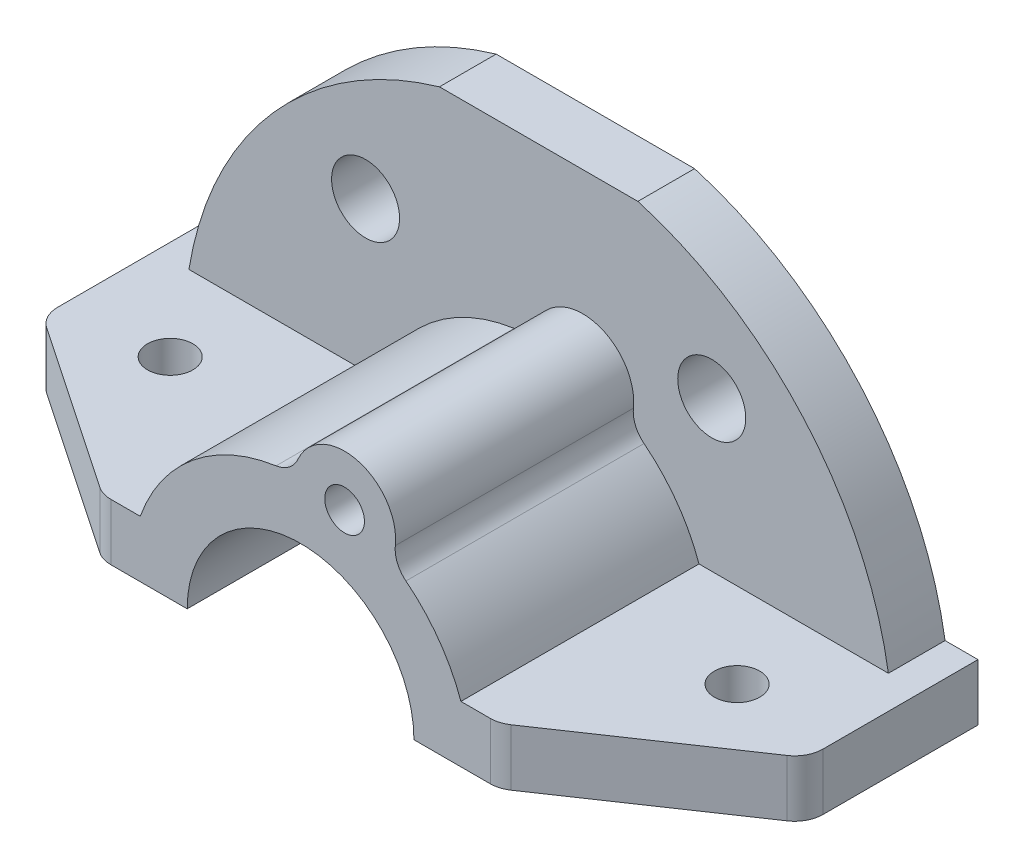
SolidWorks part; units mm, degrees
ref_plane "Front Plane" through (0, 0, 0) normal (0, 0, 1) x (1, 0, 0)
ref_plane "Top Plane" through (0, 0, 0) normal (0, 1, 0) x (1, 0, 0)
ref_plane "Right Plane" through (0, 0, 0) normal (1, 0, 0) x (0, 0, -1)
sketch "Sketch2" plane through (0, 0, 0) normal (0, 1, 0) x (1, 0, 0)
  line L0 (-67.5, -4) -> (-35, -26)
  line L1 (-67.5, -26) -> (67.5, -26)
  line L2 (-67.5, -26) -> (-67.5, 26)
  line L3 (-67.5, 26) -> (67.5, 26)
  line L4 (67.5, -26) -> (67.5, 26)
  line L5 (-67.5, -26) -> (67.5, 26) construction
  line L6 (-67.5, 26) -> (67.5, -26) construction
  line L7 (0, 0) -> (0, -19.8926) construction
  line L8 (67.5, -4) -> (35, -26)
  circle A0 centre (-50, 1) radius 4
  circle A1 centre (50, 1) radius 4
  point P0 (0, 0)
  dimension "D5" = 8
  dimension "D1" = 52
  dimension "D2" = 135
  dimension "D3" = 70
  dimension "D4" = 30
  dimension "D6" = 100
  dimension "D7" = 25
extrude "Boss-Extrude1" add sketch "Sketch2" along normal blind 10 contours L8 L4 L3 L2 L0 L1 A0 A1 region at (0, 0, -2.1349)
sketch "Sketch3" plane through (0, 0, 26) normal (0, 0, 1) x (1, 0, 0)
  line L2 (7.7646, 28.9778) -> (0, 0) construction
  line L3 (-35, 0) -> (35, 0) construction
  circle A0 centre (0, 0) radius 20
  circle A1 centre (0, 0) radius 30
  circle A2 centre (7.7646, 28.9778) radius 3.5
  circle A3 centre (7.7646, 28.9778) radius 9
  line M1 (-35, 0) -> (35, 0)
  line M3 (35, 10) -> (-35, 10)
  dimension "D1" = 40
  dimension "D2" = 60
  dimension "D3" = 7
  dimension "D4" = 18
  dimension "D5" = 75
extrude "Cut-Extrude1" cut sketch "Sketch3" against normal through all contours A0 M1 | L2 A0 M3 M1 | L2 A0 M3 M1 region at (10.2367, 4.7509, 26) region at (-8.8969, 5.0016, 26) region at (0, -8.4883, 26)
extrude "Boss-Extrude2" add sketch "Sketch3<3>" against normal up to surface (52 mm away) contours L2 A3 A1 A0 M3 | A3 L2 A0 A1 M3 | A2 L2 A3 A1 | L2 A2 A1 A3 | A1 A3 A2 | A1 A0 M3 M1 | A1 A0 M1 M3 region at (10.4819, 23.5644, 26) region at (2.7046, 25.6483, 26) region at (8.7811, 32.7714, 26) region at (18.2749, 16.6053, 26) region at (-12.8878, 19.9653, 26) region at (24.2658, 5.0755, 26) region at (-24.2658, 5.0755, 26) up to face at (43.2447, 5.0441, -26)
sketch "Sketch3<3>" plane through (0, 0, 26) normal (0, 0, 1) x (1, 0, 0) same geometry as "Sketch3"
sketch "Sketch4" plane through (0, 0, -26) normal (0, 0, -1) x (-1, 0, 0)
  line L0 (-30.5324, 36.3871) -> (30.5324, 36.3871) construction
  line L1 (0, 0) -> (0, 36.3871) construction
  line L2 (-30.5324, 36.3871) -> (0, 0) construction
  line L3 (-20, 0) -> (-67.5, 0) construction
  line L4 (17.5, 60) -> (-17.5, 60)
  line L5 (0, 60) -> (0, 0) construction
  circle A0 centre (0, 0) radius 62.5
  circle A1 centre (-30.5324, 36.3871) radius 6
  circle A2 centre (0, 0) radius 47.5 construction
  circle A3 centre (30.5324, 36.3871) radius 6
  arc M7 (-16.0101, 25.3708) -> (-28.2843, 10) centre (0, 0) ccw
  line M8 (-28.2843, 10) -> (-67.5, 10)
  line M10 (-67.5, 0) -> (-20, 0)
  arc M11 (-20, 0) -> (20, 0) centre (0, 0) cw
  line M12 (20, 0) -> (67.5, 0)
  line M14 (67.5, 10) -> (28.2843, 10)
  arc M15 (28.2843, 10) -> (1.1798, 29.9768) centre (0, 0) ccw
  arc M16 (1.1798, 29.9768) -> (-16.0101, 25.3708) centre (-7.7646, 28.9778) ccw
  circle M17 centre (-7.7646, 28.9778) radius 3.5
  dimension "D1" = 125
  dimension "D2" = 50
  dimension "D3" = 12
  dimension "D4" = 95
  dimension "D5" = 60
extrude "Boss-Extrude3" add sketch "Sketch4" against normal blind 10 contours A0 M12 M14 M15 M16 M7 M8 M10 M11 M17 | A0 L4 A1 A3 M14 M8 M7 M16 M15 region at (-0.3225, 34.3579, -26) region at (-60.9962, 4.9113, -26)
fillet "Fillet1" radius 5 6 edges at (-1.1798, 29.9768, 5) (16.0101, 25.3708, 5) (-67.5, 5, 4) (-35, 5, 26) (67.5, 5, 4) (35, 5, 26)
